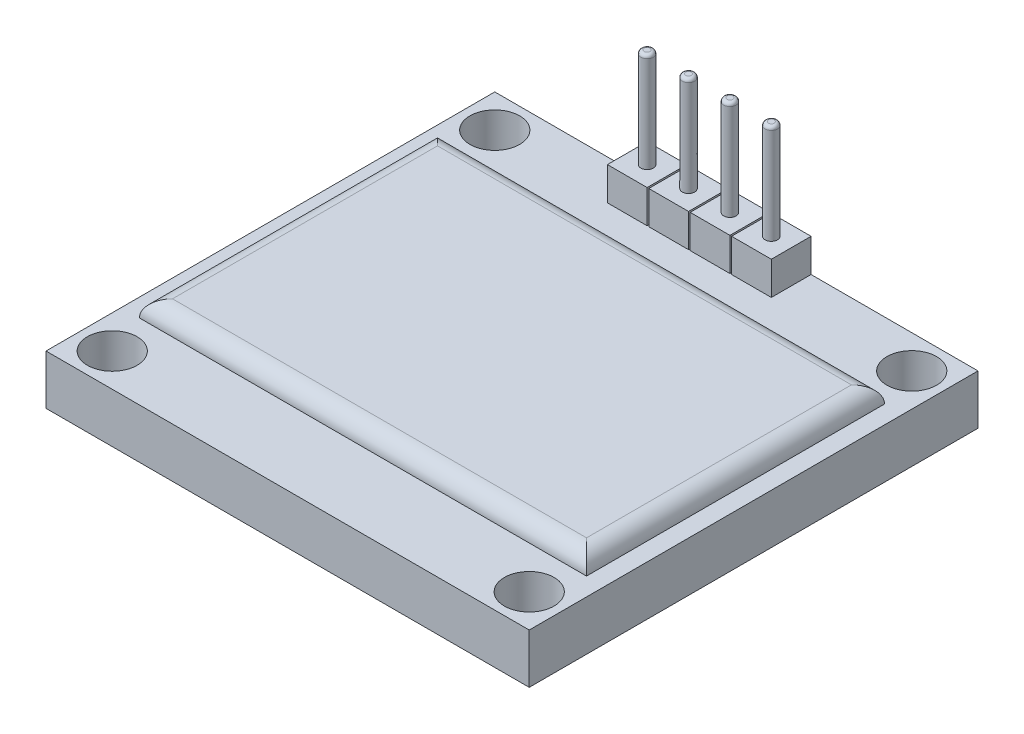
SolidWorks part; units mm, degrees
ref_plane "Front Plane" through (0, 0, 0) normal (0, 0, 1) x (1, 0, 0)
ref_plane "Top Plane" through (0, 0, 0) normal (0, 1, 0) x (1, 0, 0)
ref_plane "Right Plane" through (0, 0, 0) normal (1, 0, 0) x (0, 0, -1)
sketch "Sketch1" plane through (0, 0, 0) normal (0, 1, 0) x (1, 0, 0)
  line L1 (14.59, -13.55) -> (-14.59, -13.55)
  line L2 (14.59, -13.55) -> (14.59, 13.55)
  line L3 (14.59, 13.55) -> (-14.59, 13.55)
  line L4 (-14.59, -13.55) -> (-14.59, 13.55)
  line L5 (14.59, -13.55) -> (-14.59, 13.55) construction
  line L6 (14.59, 13.55) -> (-14.59, -13.55) construction
  point P0 (0, 0)
  dimension "D1" = 29.18
  dimension "D2" = 27.1
extrude "Boss-Extrude1" add sketch "Sketch1" along normal blind 3
sketch "Sketch2" plane through (0, 3, 0) normal (0, 1, 0) x (1, 0, 0)
  line L1 (13.5, -9) -> (-13.5, -9)
  line L2 (13.5, -9) -> (13.5, 9)
  line L3 (13.5, 9) -> (-13.5, 9)
  line L4 (-13.5, -9) -> (-13.5, 9)
  line L5 (13.5, -9) -> (-13.5, 9) construction
  line L6 (13.5, 9) -> (-13.5, -9) construction
  point P0 (0, 0)
  dimension "D1" = 18
  dimension "D2" = 27
extrude "Boss-Extrude2" add sketch "Sketch2" along normal blind 1
fillet "Fillet1" radius 1 4 edges at (0, 4, -9) (13.5, 4, 0) (0, 4, 9) (-13.5, 4, 0)
sketch "Sketch3" plane through (0, 3, 0) normal (0, 1, 0) x (1, 0, 0)
  line L0 (14.59, 13.55) -> (-14.59, 13.55) construction
  line L1 (-14.59, 13.55) -> (-14.59, -13.55) construction
  line L2 (14.59, -13.55) -> (14.59, 13.55) construction
  line L3 (0, 0) -> (14.59, 0) construction
  circle A0 centre (-12.59, 11.55) radius 1.5
  circle A1 centre (12.59, 11.55) radius 1.5
  circle A2 centre (12.59, -11.55) radius 1.5
  circle A3 centre (-12.59, -11.55) radius 1.5
  dimension "D1" = 3
  dimension "D2" = 3
  dimension "D6" = 2
  dimension "D3" = 2
  dimension "D4" = 2
  dimension "D5" = 2
extrude "Cut-Extrude1" cut sketch "Sketch3" against normal through all
sketch "Sketch4" plane through (0, 3, 0) normal (0, 1, 0) x (1, 0, 0)
  line L0 (14.59, 13.55) -> (-14.59, 13.55) construction
  line L1 (-5.39, 11.15) -> (-2.99, 11.15)
  line L2 (-5.39, 11.15) -> (-5.39, 13.55)
  line L3 (-5.39, 13.55) -> (-2.99, 13.55)
  line L4 (-2.99, 11.15) -> (-2.99, 13.55)
  line L5 (-5.39, 11.15) -> (-2.99, 13.55) construction
  line L6 (-5.39, 13.55) -> (-2.99, 11.15) construction
  line L7 (-14.59, 13.55) -> (-14.59, -13.55) construction
  line L8 (-2.89, 13.55) -> (-0.49, 13.55)
  line L9 (-0.49, 11.15) -> (-0.49, 13.55)
  line L10 (-2.89, 11.15) -> (-0.49, 11.15)
  line L11 (-2.89, 11.15) -> (-2.89, 13.55)
  line L12 (-0.39, 13.55) -> (2.01, 13.55)
  line L13 (2.01, 11.15) -> (2.01, 13.55)
  line L14 (-0.39, 11.15) -> (2.01, 11.15)
  line L15 (-0.39, 11.15) -> (-0.39, 13.55)
  line L16 (2.11, 13.55) -> (4.51, 13.55)
  line L17 (4.51, 11.15) -> (4.51, 13.55)
  line L18 (2.11, 11.15) -> (4.51, 11.15)
  line L19 (2.11, 11.15) -> (2.11, 13.55)
  point P0 (-4.19, 12.35)
  dimension "D1" = 2.4
  dimension "D2" = 2.4
  dimension "D3" = 0
  dimension "D4" = 9.2
  dimension "D5" = 4
extrude "Boss-Extrude3" add sketch "Sketch4" along normal blind 2
sketch "Sketch5" plane through (0, 5, 0) normal (0, 1, 0) x (1, 0, 0)
  line L0 (-5.39, 13.55) -> (-5.39, 11.15) construction
  line L1 (-5.39, 11.15) -> (-2.99, 11.15) construction
  circle A0 centre (-4.19, 12.35) radius 0.375
  circle A1 centre (-1.69, 12.35) radius 0.375
  circle A2 centre (0.81, 12.35) radius 0.375
  circle A3 centre (3.31, 12.35) radius 0.375
  point P2 (-5.39, 12.35)
  dimension "D1" = 0.75
  dimension "D2" = 1.2
  dimension "D3" = 1.2
  dimension "D4" = 4
extrude "Boss-Extrude4" add sketch "Sketch5" along normal blind 6
fillet "Fillet2" radius 0.2 4 edges at (3.31, 11, -11.975) (0.81, 11, -11.975) (-1.69, 11, -11.975) (-4.19, 11, -11.975)
